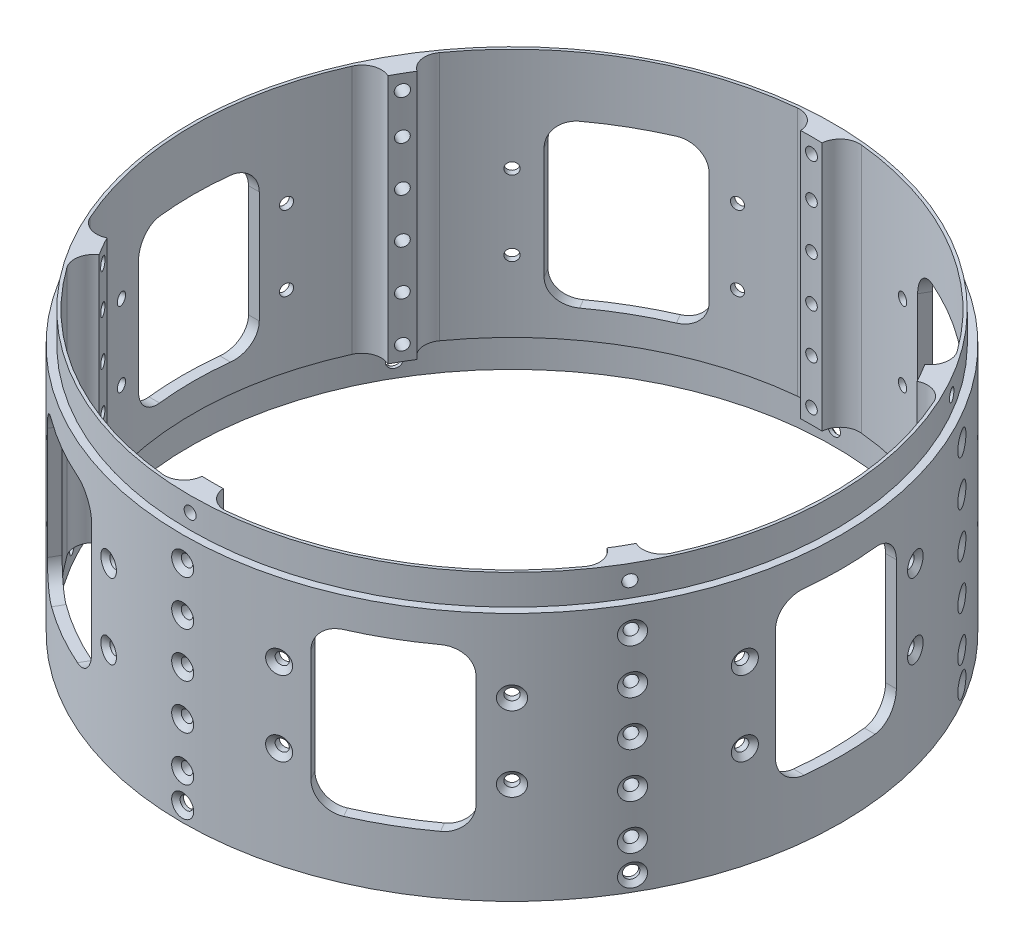
SolidWorks part; units mm, degrees
material "6061-T6 (SS)"
ref_plane "Front Plane" through (0, 0, 0) normal (0, 0, 1) x (1, 0, 0)
ref_plane "Top Plane" through (0, 0, 0) normal (0, 1, 0) x (1, 0, 0)
ref_plane "Right Plane" through (0, 0, 0) normal (1, 0, 0) x (0, 0, -1)
sketch "Sketch1" plane through (0, 0, 0) normal (0, 0, 1) x (1, 0, 0)
  line L0 (0, 42.3951) -> (0, -32.8937) construction
  line L1 (0, -35.6235) -> (0, 35.6235) construction
  line L2 (76.2, -63.5) -> (76.2, 0)
  line L3 (76.2, 0) -> (81.8896, 0)
  line L4 (81.8896, 0) -> (81.8896, -7.6708)
  line L5 (81.8896, -7.6708) -> (83.82, -7.6708)
  line L6 (83.82, -7.6708) -> (83.82, -71.12)
  line L7 (83.82, -71.12) -> (81.9404, -71.12)
  line L8 (81.9404, -71.12) -> (81.9404, -63.5)
  line L9 (81.9404, -63.5) -> (76.2, -63.5)
  line L10 (81.8896, -7.62) -> (84.2911, -7.62) construction
  dimension "D5" = 5.6896
  dimension "D10" = 76.2
  dimension "D2" = 7.62
  dimension "D4" = 7.62
  dimension "D6" = 7.62
revolve "Revolve1" add sketch "Sketch1" angle 360 about L0
sketch "Sketch2" plane through (0, 0, 0) normal (0, 1, 0) x (1, 0, 0)
  line L0 (0, 0) -> (0, 112.6688) construction
  line L1 (0, -35.6235) -> (0, 35.6235) construction
  line L2 (0, 0) -> (-128.6689, 74.287) construction
  line L3 (0, 0) -> (-50.2561, 87.0461) construction
  line L4 (0, 0) -> (-7.6343, 75.8166) construction
  arc A0 (-7.6343, 75.8166) -> (-61.8419, 44.5198) centre (0, 0) ccw construction
  arc A1 (-8.128, 80.7194) -> (-65.841, 47.3988) centre (0, 0) ccw
  arc A2 (-7.1406, 70.9138) -> (-57.8428, 41.6409) centre (0, 0) ccw
  arc A3 (-7.1406, 70.9138) -> (-8.128, 80.7194) centre (-7.6343, 75.8166) ccw
  arc A4 (-65.841, 47.3988) -> (-57.8428, 41.6409) centre (-61.8419, 44.5198) ccw
  circle A5 centre (0, 0) radius 81.8896 construction
  circle A7 centre (0, 0) radius 76.2 construction
  point P5 (-38.1, 65.9911)
  dimension "D2" = 0.762
  dimension "D1" = 60
  dimension "D3" = 30
  dimension "D4" = 5.75
extrude "Cut-Extrude1" cut sketch "Sketch2" against normal through all
pattern_circular "CirPattern1" count 6 over 360 about axis through (0, 42.3951, 0) along (0, 1, 0) of "Cut-Extrude1"
ref_plane "Plane1" through (0, 0, 83.82) normal (0, 0, 1) x (1, 0, 0)
hole_wizard "Tapped Hole for #4-40 Helicoil1" positions "Sketch3" profile "Sketch4" tap size "#4-40" standard "Helicoil® Inch"
sketch "Sketch3" plane through (0, 0, 83.82) normal (0, 0, 1) x (1, 0, 0)
  line L0 (81.8896, 0) -> (-81.8896, 0) construction
  line L1 (2.7181, 0) -> (-2.7181, 0) construction
  line L2 (2.7181, 0) -> (-2.7181, 0) construction
  line L3 (0, 0) -> (0, -3.81) construction
  line L5 (-2.7181, -63.5) -> (2.7181, -63.5) construction
  line L6 (-2.7181, -63.5) -> (2.7181, -63.5) construction
  line L7 (0, -63.5) -> (0, -59.69) construction
  point P0 (0, -3.81)
  point P21 (0, 0)
  dimension "D1" = 3.81
  dimension "D2" = 3.81
cosmetic thread "Hole Thread6" parameters "D1"=3.556, "D2"=3.7414
sketch "Sketch4" plane through (0, -3.81, 83.82) normal (1, 0, 0) x (0, -1, 0)
  line L0 (0, 0) -> (0, 26.3157)
  line L1 (0, 26.3157) -> (1.524, 25.4)
  line L2 (1.524, 25.4) -> (1.524, 0)
  line L5 (1.524, 0) -> (0, 0)
  line L10 (0, 26.3157) -> (-1.524, 25.4) construction
  line L11 (0, -6.35) -> (0, 107.95) construction
  dimension "Tap Drill Dia." = 3.048
  dimension "Tap Drill Depth" = 25.4
  dimension "Drill Angle" = 118
hole_wizard "CSK for #4 Flat Head Machine Screw (100)1" positions "Sketch5" profile "Sketch6" countersink size "#4" standard "ANSI Inch"
sketch "Sketch5" plane through (0, 0, 83.82) normal (0, 0, 1) x (1, 0, 0)
  line L0 (-2.7181, -63.5) -> (2.7181, -63.5) construction
  line L1 (-2.7181, -63.5) -> (2.7181, -63.5) construction
  line L2 (0, -63.5) -> (0, -67.31) construction
  point P0 (0, -67.31)
  dimension "D1" = 3.81
sketch "Sketch6" plane through (0, -67.31, 83.82) normal (1, 0, 0) x (0, -1, 0)
  line L0 (0, 0) -> (0, 26.3806)
  line L1 (0, 26.3806) -> (1.6319, 25.4)
  line L2 (1.6319, 25.4) -> (1.6319, 1.0284)
  line L3 (1.6319, 1.0284) -> (2.8575, 0)
  line L5 (2.8575, 0) -> (0, 0)
  line L6 (-1.6319, 1.0284) -> (-2.8575, 0) construction
  line L10 (0, 26.3806) -> (-1.632, 25.4) construction
  line L11 (0, -6.35) -> (0, 107.95) construction
  dimension "Hole Dia." = 3.2639
  dimension "Hole Depth" = 25.4
  dimension "Near C'Sink Dia." = 5.715
  dimension "Near C'Sink Angle" = 100
  dimension "Drill Angle" = 118
hole_wizard "CSK for #4 Flat Head Machine Screw (100)3" positions "Sketch12" profile "Sketch13" countersink size "#4" standard "ANSI Inch"
sketch "Sketch12" plane through (0, 0, 83.82) normal (0, 0, 1) x (1, 0, 0)
  line L0 (-2.7181, -63.5) -> (2.7181, -63.5) construction
  line L3 (0, 0) -> (0, -63.5) construction
  line L5 (2.7181, 0) -> (-2.7181, 0) construction
  point P19 (0, -59.69)
  point P50 (0, -48.26)
  point P51 (0, -36.83)
  point P52 (0, -25.4)
  point P53 (0, -13.97)
  dimension "D1" = 3.81
  dimension "D2" = 5
other "AlignGroup1"
sketch "Sketch13" plane through (0, -59.69, 83.82) normal (1, 0, 0) x (0, -1, 0)
  line L0 (0, 0) -> (0, 26.2852)
  line L1 (0, 26.2852) -> (1.4732, 25.4)
  line L2 (1.4732, 25.4) -> (1.4732, 1.1616)
  line L3 (1.4732, 1.1616) -> (2.8575, 0)
  line L5 (2.8575, 0) -> (0, 0)
  line L6 (-1.4732, 1.1616) -> (-2.8575, 0) construction
  line L10 (0, 26.2852) -> (-1.4732, 25.4) construction
  line L11 (0, -6.35) -> (0, 107.95) construction
  dimension "Hole Dia." = 2.9464
  dimension "Hole Depth" = 25.4
  dimension "Near C'Sink Dia." = 5.715
  dimension "Near C'Sink Angle" = 100
  dimension "Drill Angle" = 118
pattern_circular "CirPattern2" count 6 over 360 about axis through (0, 42.3951, 0) along (0, 1, 0) of "Tapped Hole for #4-40 Helicoil1", "CSK for #4 Flat Head Machine Screw (100)1", "CSK for #4 Flat Head Machine Screw (100)3"
sketch "Sketch7" plane through (0, 0, 0) normal (1, 0, 0) x (0, 0, -1)
  line L1 (-9.017, -15.24) -> (9.017, -15.24)
  line L2 (-15.367, -21.59) -> (-15.367, -50.038)
  line L3 (-9.017, -56.388) -> (9.017, -56.388)
  line L4 (15.367, -21.59) -> (15.367, -50.038)
  line L5 (-15.367, -15.24) -> (15.367, -56.388) construction
  line L6 (-15.367, -56.388) -> (15.367, -15.24) construction
  arc A0 (-15.367, -50.038) -> (-9.017, -56.388) centre (-9.017, -50.038) ccw
  arc A1 (9.017, -56.388) -> (15.367, -50.038) centre (9.017, -50.038) ccw
  arc A2 (15.367, -21.59) -> (9.017, -15.24) centre (9.017, -21.59) ccw
  arc A3 (-9.017, -15.24) -> (-15.367, -21.59) centre (-9.017, -21.59) ccw
  point P0 (0, -35.814)
  dimension "D4" = 6.35
  dimension "D1" = 41.148
  dimension "D2" = 30.734
  dimension "D3" = 15.24
extrude "Cut-Extrude2" cut sketch "Sketch7" against normal through all
sketch "Sketch9" plane through (0, -7.6708, 0) normal (0, 1, 0) x (1, 0, 0)
  line L0 (-49.5, 0) -> (-83.82, 0)
  line L1 (-50.2347, -13.4603) -> (-80.9639, -21.6942)
  line L2 (-83.82, 11.0351) -> (-83.82, -11.0351) construction
  line L3 (-83.82, -11.0351) -> (-78.1078, -32.3533) construction
  arc A0 (-83.3336, 9.017) -> (-83.3336, -9.017) centre (0, 0) ccw construction
  circle A1 centre (0, 0) radius 83.82 construction
  dimension "D1" = 15
ref_plane "Plane3" through (-80.9639, -7.6708, 21.6942) normal (-0.9659, 0, 0.2588) x (0.2588, 0, 0.9659)
hole_wizard "CSK for #4 Flat Head Machine Screw (100)2" positions "Sketch10" profile "Sketch11" countersink size "#4" standard "ANSI Inch"
sketch "Sketch10" plane through (-80.9639, -7.6708, 21.6942) normal (-0.9659, 0, 0.2588) x (0.2588, 0, 0.9659)
  line L0 (0, 0) -> (0, -18.6182) construction
  line L1 (0, -18.6182) -> (0, -37.6682) construction
  line L5 (0, -28.1432) -> (-6.4831, -28.1432) construction
  line L8 (-6.4831, -13.9192) -> (-6.4831, -42.3672) construction
  point P0 (0, -18.6182)
  point P2 (0, -37.6682)
  dimension "D1" = 19.05
sketch "Sketch11" plane through (-80.9639, -26.289, 21.6942) normal (0, 1, 0) x (0.2588, 0, 0.9659)
  line L0 (0, 0) -> (0, 26.2852)
  line L1 (0, 26.2852) -> (1.4732, 25.4)
  line L2 (1.4732, 25.4) -> (1.4732, 1.1616)
  line L3 (1.4732, 1.1616) -> (2.8575, 0)
  line L5 (2.8575, 0) -> (0, 0)
  line L6 (-1.4732, 1.1616) -> (-2.8575, 0) construction
  line L10 (0, 26.2852) -> (-1.4732, 25.4) construction
  line L11 (0, -6.35) -> (0, 107.95) construction
  dimension "Hole Dia." = 2.9464
  dimension "Hole Depth" = 25.4
  dimension "Near C'Sink Dia." = 5.715
  dimension "Near C'Sink Angle" = 100
  dimension "Drill Angle" = 118
mirror "Mirror1" about plane through (0, 0, 0) normal (0, 0, 1) of "CSK for #4 Flat Head Machine Screw (100)2"
pattern_circular "CirPattern5" count 6 over 360 about axis through (0, -7.6708, 0) along (0, 1, 0) of "Cut-Extrude2", "Mirror1"
ref_plane "Plane2" [suppressed] through (0, 0, 0) normal (-0.7071, 0, 0.7071) x (0.7071, 0, 0.7071)
sketch "Sketch8" [suppressed] plane through (0, 0, 0) normal (-0.7071, 0, 0.7071) x (0.7071, 0, 0.7071)
  line L0 (0, 0) -> (89.1919, 0) construction
  line L1 (-9.017, -17.145) -> (-6.858, -17.145)
  line L2 (-12.192, -20.32) -> (-12.192, -31.115)
  line L3 (-9.017, -34.29) -> (-6.858, -34.29)
  line L4 (-3.683, -20.32) -> (-3.683, -31.115)
  line L5 (0, 0) -> (0, -89.2767) construction
  line L6 (-83.82, -71.12) -> (83.82, -71.12) construction
  line L7 (-7.9375, -52.07) -> (-4.7625, -52.07)
  line L8 (-9.525, -53.6575) -> (-9.525, -56.8325)
  line L9 (-7.9375, -58.42) -> (-4.7625, -58.42)
  line L10 (-3.175, -53.6575) -> (-3.175, -56.8325)
  arc A0 (-9.017, -34.29) -> (-12.192, -31.115) centre (-9.017, -31.115) cw
  arc A1 (-3.683, -31.115) -> (-6.858, -34.29) centre (-6.858, -31.115) cw
  arc A2 (-3.683, -20.32) -> (-6.858, -17.145) centre (-6.858, -20.32) ccw
  arc A3 (-9.017, -17.145) -> (-12.192, -20.32) centre (-9.017, -20.32) ccw
  arc A4 (-9.525, -56.8325) -> (-7.9375, -58.42) centre (-7.9375, -56.8325) ccw
  arc A5 (-3.175, -56.8325) -> (-4.7625, -58.42) centre (-4.7625, -56.8325) cw
  arc A6 (-3.175, -53.6575) -> (-4.7625, -52.07) centre (-4.7625, -53.6575) ccw
  arc A7 (-7.9375, -52.07) -> (-9.525, -53.6575) centre (-7.9375, -53.6575) ccw
  circle A8 centre (-6.35, -48.895) radius 1.5875
  circle A9 centre (-6.35, -61.595) radius 1.5875
  point P20 (-3.175, -55.245)
  point P29 (-6.35, -58.42)
  dimension "D1" = 3.175
  dimension "D8" = 1.5875
  dimension "D11" = 3.175
  dimension "D12" = 3.175
  dimension "D2" = 8.509
  dimension "D3" = 17.145
  dimension "D4" = 17.145
  dimension "D5" = 3.683
  dimension "D6" = 6.35
  dimension "D7" = 6.35
  dimension "D9" = 6.35
  dimension "D10" = 12.7
  dimension "D13" = 3.175
  dimension "D14" = 3.175
extrude "Cut-Extrude3" [suppressed] cut sketch "Sketch8" along normal through all
equation "\"nominalLength\"=2.5"
equation "\"D8@Sketch1\"=\"nominalLength\""
equation "\"D12@Sketch8\"=\"D11@Sketch8\""
